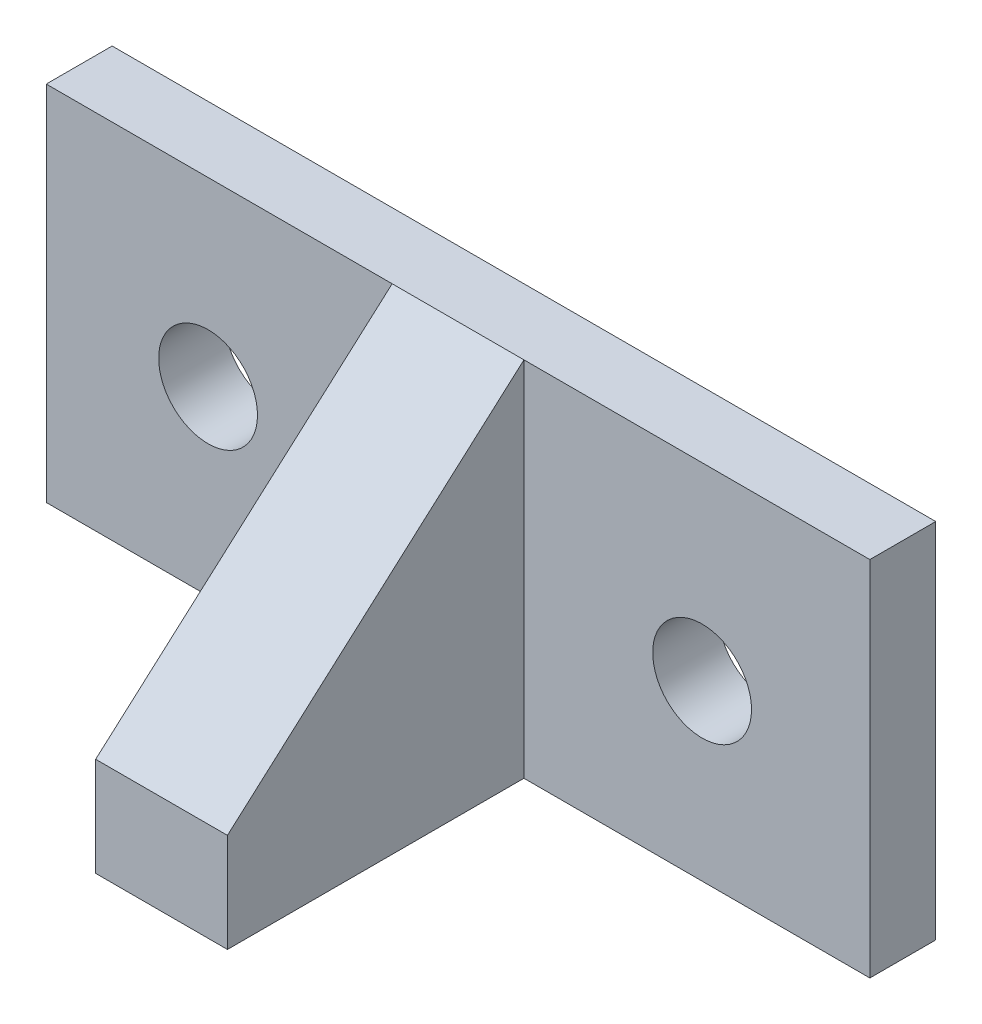
SolidWorks part; units mm, degrees
ref_plane "Front Plane" through (0, 0, 0) normal (0, 0, 1) x (1, 0, 0)
ref_plane "Top Plane" through (0, 0, 0) normal (0, 1, 0) x (1, 0, 0)
ref_plane "Right Plane" through (0, 0, 0) normal (1, 0, 0) x (0, 0, -1)
sketch "Sketch1" plane through (0, 0, 0) normal (1, 0, 0) x (0, 0, -1)
  line L0 (0, 0) -> (0, 27.5)
  line L1 (0, 0) -> (0, -27.5)
  line L2 (0, -27.5) -> (-55, -27.5)
  line L3 (-55, -27.5) -> (-55, -12.5)
  line L5 (0, 27.5) -> (-10, 27.5)
  line L6 (-10, 27.5) -> (-10, -27.5)
  line L7 (-55, -12.5) -> (-10, 27.5)
  point P8 (0, 0)
extrude "Boss-Extrude1" add sketch "Sketch1" against normal blind 125 contours L7 L3 L2 L6 | L5 L6 L2 L1 L0 region at (0, 0, 5) region at (0, -8.0952, 28.2143)
extrude "Cut-Extrude1" cut sketch "Sketch1<3>" against normal blind 52.5 contours L7 L3 L2 L6 region at (0, -8.0952, 28.2143)
sketch "Sketch1<3>" plane through (0, 0, 0) normal (1, 0, 0) x (0, 0, -1) same geometry as "Sketch1"
extrude "Cut-Extrude2" cut sketch "Sketch1<4>" along normal blind 52.5 from surface contours L7 L3 L2 L6 region at (0, -8.0952, 28.2143) starting at face at (-125, -2.5, 24)
sketch "Sketch1<4>" plane through (0, 0, 0) normal (1, 0, 0) x (0, 0, -1) same geometry as "Sketch1"
sketch "Sketch3" plane through (0, 0, 10) normal (0, 0, 1) x (1, 0, 0)
  line L0 (-125, 0) -> (-62.9392, 0)
  line L1 (-125, 27.5) -> (-125, -27.5) construction
  line L2 (-62.9392, 0) -> (-100.4392, 0)
  line L3 (-62.9392, 0) -> (-62.5, 27.5)
  line L4 (-72.5, 27.5) -> (-52.5, 27.5) construction
  circle A0 centre (-100.4392, 0) radius 7.5
  circle A1 centre (-25.4583, -1.1975) radius 7.5
extrude "Cut-Extrude3" cut sketch "Sketch3" against normal blind 10 contours L0 A0 | L0 A0 | A1 region at (-100.4392, 3.1831, 10) region at (-100.4392, -3.1831, 10) region at (-25.4583, -1.1975, 10)
